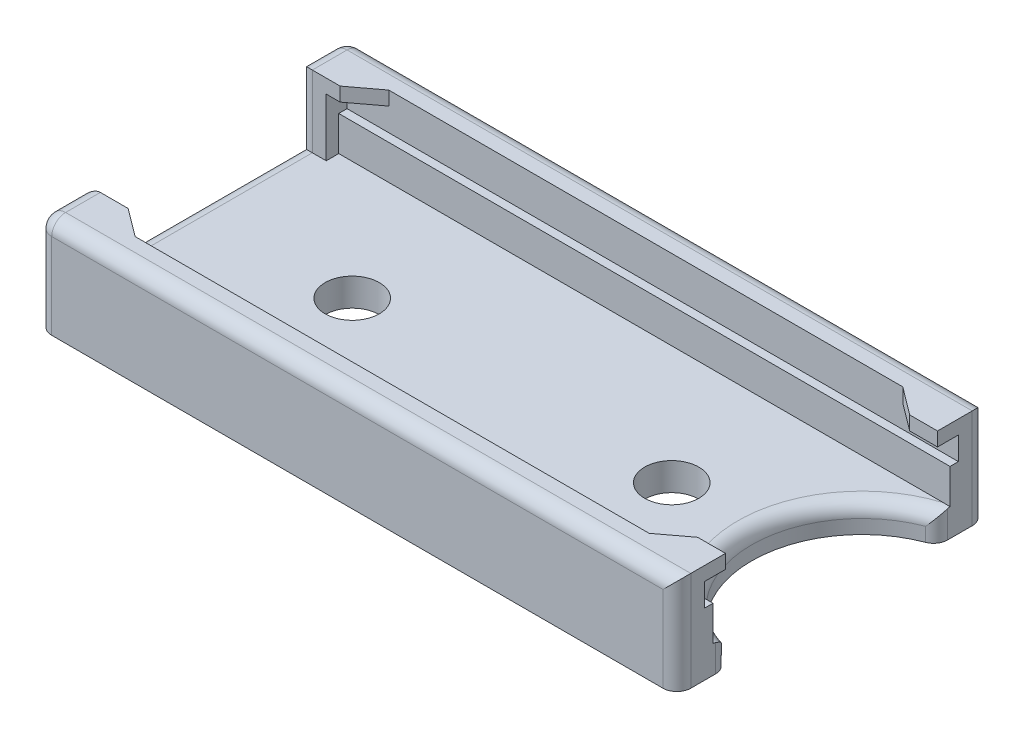
SolidWorks part; units mm, degrees
ref_plane "Plano frontal" through (0, 0, 0) normal (0, 0, 1) x (1, 0, 0)
ref_plane "Plano superior" through (0, 0, 0) normal (0, 1, 0) x (1, 0, 0)
ref_plane "Plano direito" through (0, 0, 0) normal (1, 0, 0) x (0, 0, -1)
sketch "Base" plane through (0, 0, 0) normal (0, 1, 0) x (1, 0, 0)
  line L1 (-23, 11.13) -> (23, 11.13)
  line L2 (-23, 11.13) -> (-23, -11.13)
  line L3 (-23, -11.13) -> (23, -11.13)
  line L4 (23, 11.13) -> (23, -11.13)
  line L5 (-23, 11.13) -> (23, -11.13) construction
  line L6 (-23, -11.13) -> (23, 11.13) construction
  point P0 (0, 0)
  dimension "D1" = 22.26
  dimension "D2" = 46
extrude "Ressalto-extrusão1" add sketch "Base" against normal blind 2
sketch "Parede_Ext" plane through (0, 0, 0) normal (0, 1, 0) x (1, 0, 0)
  line L0 (-23, -11.13) -> (23, -11.13) construction
  line L1 (-23, 11.13) -> (-23, -11.13) construction
  line L2 (23, 11.13) -> (-23, 11.13) construction
  line L3 (-23, -11.13) -> (23, -11.13)
  line L4 (-23, 11.13) -> (-23, 7.63)
  line L5 (23, 11.13) -> (-23, 11.13)
  line L6 (23, 9.13) -> (-21, 9.13)
  line L7 (-21, 9.13) -> (-21, 7.63)
  line L8 (-21, -9.13) -> (23, -9.13)
  line L9 (23, 11.13) -> (23, 9.13)
  line L10 (23, -9.13) -> (23, -11.13)
  line L11 (-23, 7.63) -> (-21, 7.63)
  line L12 (0, 0) -> (-4.5152, 0) construction
  line L13 (-23, -7.63) -> (-21, -7.63)
  line L14 (-21, 7.63) -> (-21, -7.63) construction
  line L15 (-21, -7.63) -> (-21, -9.13)
  line L16 (-21, 9.13) -> (-21, -9.13) construction
  line L17 (-23, 7.63) -> (-23, -7.63) construction
  line L18 (-23, -7.63) -> (-23, -11.13)
  line L19 (-23, 11.13) -> (-23, -11.13) construction
  dimension "D2" = 3.5
  dimension "D1" = 2
extrude "Ressalto-extrusão2" add sketch "Parede_Ext" along normal blind 5.16
sketch "Parede_Int" plane through (0, 0, 0) normal (0, 1, 0) x (1, 0, 0)
  line L0 (23, -9.13) -> (-21, -9.13) construction
  line L1 (-21, 9.13) -> (23, 9.13) construction
  line L2 (23, -9.13) -> (-21, -9.13)
  line L3 (-21, 9.13) -> (23, 9.13)
  line L4 (-21, 8.53) -> (23, 8.53)
  line L5 (23, -8.53) -> (-21, -8.53)
  line L6 (23, 9.13) -> (23, 8.53)
  line L7 (23, -8.53) -> (23, -9.13)
  line L8 (-21, 9.13) -> (-21, 8.53)
  line L9 (-21, -8.53) -> (-21, -9.13)
  dimension "D1" = 0.6
extrude "Ressalto-extrusão3" add sketch "Parede_Int" along normal blind 2.5
sketch "Esboço4" plane through (0, 5.16, 0) normal (0, 1, 0) x (1, 0, 0)
  line L0 (-21, 7.63) -> (-20, 7.63)
  line L1 (-20, 7.63) -> (-18, 9.13)
  line L2 (-21, 9.13) -> (23, 9.13) construction
  line L3 (-21, 7.63) -> (-21, 9.13)
  line L4 (-21, 9.13) -> (-18, 9.13)
  line L5 (23, 9.13) -> (23, 7.63)
  line L6 (23, -8.53) -> (23, 8.53) construction
  line L7 (23, 7.63) -> (21, 7.63)
  line L8 (21, 7.63) -> (19, 9.13)
  line L9 (23, 9.13) -> (-21, 9.13) construction
  line L10 (23, 9.13) -> (19, 9.13)
  line L11 (0, 0) -> (-6.9599, 0) construction
  line L12 (23, -9.13) -> (23, -7.63)
  line L13 (23, -7.63) -> (21, -7.63)
  line L14 (21, -7.63) -> (19, -9.13)
  line L15 (23, -9.13) -> (19, -9.13)
  line L16 (-21, -7.63) -> (-21, -9.13)
  line L17 (-21, -7.63) -> (-20, -7.63)
  line L18 (-20, -7.63) -> (-18, -9.13)
  line L19 (-21, -9.13) -> (-18, -9.13)
  dimension "D3" = 1.5
  dimension "D4" = 1.5
  dimension "D5" = 2
  dimension "D6" = 2
extrude "Ressalto-extrusão4" add sketch "Esboço4" against normal blind 1
sketch "Furos" plane through (0, 0, 0) normal (0, 1, 0) x (1, 0, 0)
  line L0 (0, 0) -> (0, -11.13) construction
  line L1 (-23, -11.13) -> (23, -11.13) construction
  line L2 (0, 0) -> (23, 0) construction
  line L3 (23, -8.53) -> (23, 8.53) construction
  circle A0 centre (11.5, 0) radius 1.95
  circle A1 centre (-11.5, 0) radius 1.95
  dimension "D1" = 3.9
extrude "Corte-extrusão1" cut sketch "Furos" against normal up to surface (2 mm away) up to face at (0, -2, 0)
sketch "Esboço5" plane through (0, 0, 0) normal (0, 1, 0) x (1, 0, 0)
  line L0 (23, -8.53) -> (23, 8.53) construction
  line L1 (23, -8.53) -> (23, 8.53)
  line L2 (11.5, 0) -> (23, 0) construction
  line L3 (17.25, 0) -> (17.25, -2.421) construction
  circle A0 centre (11.5, 0) radius 1.95 construction
  circle A1 centre (11.5, 0) radius 1.95 construction
  arc A3 (23, 7.63) -> (23, -7.63) centre (25.1873, 0) ccw
  arc A4 (23, -7.63) -> (23, 7.63) centre (25.1873, 0) ccw construction
extrude "Corte-extrusão2" cut sketch "Esboço5" against normal through all contours L1 A3 region at (20.6092, 0, 0)
fillet "Filete1" radius 1 14 edges at (23, -1, 7.63) (23, -1, -7.63) (17.25, 0, 0) (-23, 2.58, 7.63) (-23, 2.58, -7.63) (-23, 0, 0) (-23, 5.16, -9.38) (-23, 1.58, -11.13) (-23, 1.58, 11.13) (-23, 5.16, 9.38) (0, 5.16, -11.13) (23, 1.58, -11.13) (23, 1.58, 11.13) (0, 5.16, 11.13)
equation "\"D1@Base\"=18 + 4+ .26"
equation "\"D2@Base\" = 42.5 + 1.5 + 2"
equation "\"D4@Esboço4\"=\"D3@Esboço4\""
